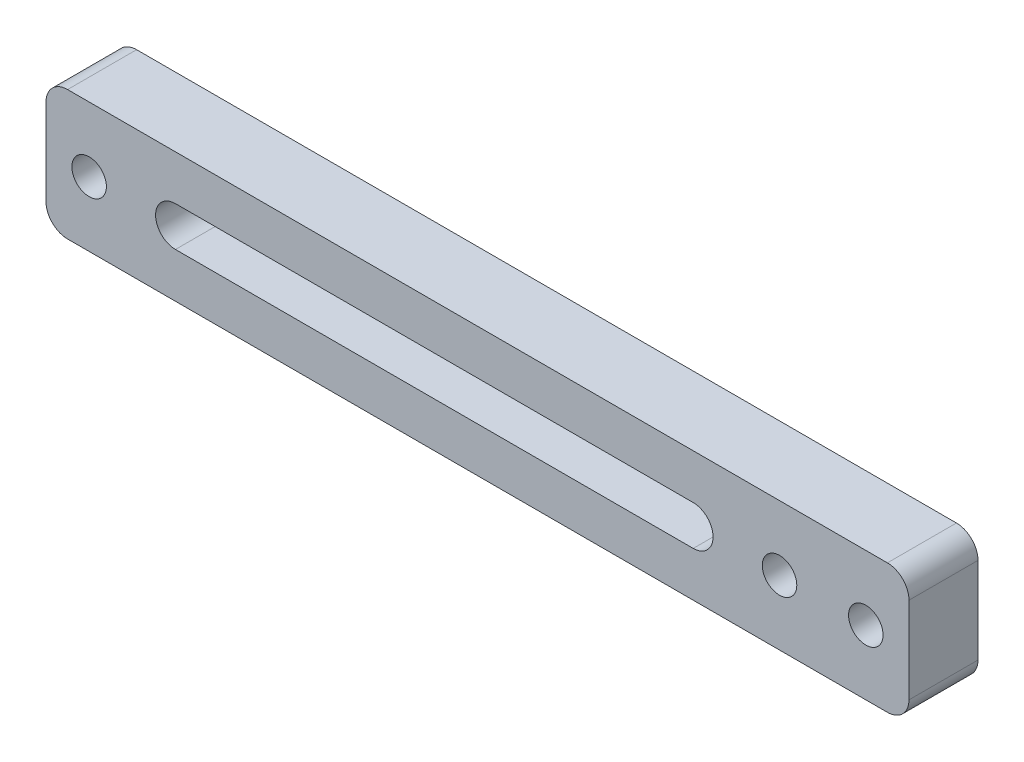
SolidWorks part; units mm, degrees
ref_plane "Спереди" through (0, 0, 0) normal (0, 0, 1) x (1, 0, 0)
ref_plane "Сверху" through (0, 0, 0) normal (0, 1, 0) x (1, 0, 0)
ref_plane "Справа" through (0, 0, 0) normal (1, 0, 0) x (0, 0, -1)
sketch "Эскиз1" plane through (0, 0, 0) normal (0, 0, 1) x (1, 0, 0)
  line L1 (0, 0) -> (100, 0)
  line L2 (0, 0) -> (0, 15)
  line L3 (0, 15) -> (100, 15)
  line L4 (100, 0) -> (100, 15)
  dimension "D1" = 100
  dimension "D2" = 15
extrude "Вытянуть1" add sketch "Эскиз1" along normal blind 8
sketch "Эскиз2" plane through (0, 0, 8) normal (0, 0, 1) x (1, 0, 0)
  line L0 (0, 15) -> (0, 0) construction
  line L1 (15, 9.8) -> (75, 9.8)
  line L3 (15, 5.2) -> (75, 5.2)
  line L4 (100, 0) -> (100, 15) construction
  line L5 (-14.6814, 7.5) -> (66.4971, 7.5) construction
  circle A0 centre (5, 7.5) radius 2
  arc A1 (75, 9.8) -> (75, 5.2) centre (75, 7.5) cw
  arc A2 (15, 9.8) -> (15, 5.2) centre (15, 7.5) ccw
  circle A3 centre (95, 7.5) radius 2
  circle A4 centre (85, 7.5) radius 2
  point P9 (0, 7.5)
  dimension "D4" = 4
  dimension "D1" = 5.2
  dimension "D2" = 5
  dimension "D3" = 10
  dimension "D5" = 10
  dimension "D6" = 5
  dimension "D7" = 10
extrude "Вытянуть2" cut sketch "Эскиз2" against normal blind 8
fillet "Скругление2" radius 2.5 4 edges at (0, 0, 4) (0, 15, 4) (100, 0, 4) (100, 15, 4)
